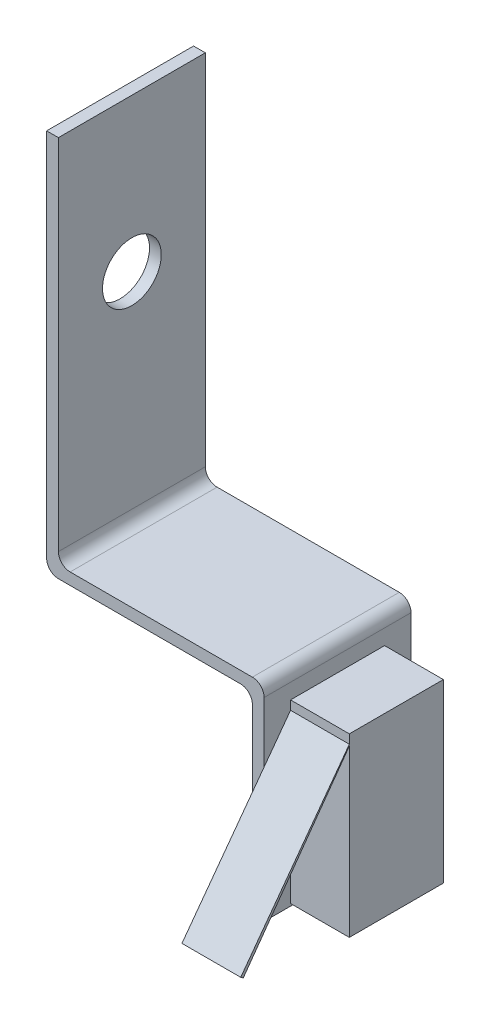
SolidWorks part; units mm, degrees
ref_plane "Alzado" through (0, 0, 0) normal (0, 0, 1) x (1, 0, 0)
ref_plane "Planta" through (0, 0, 0) normal (0, 1, 0) x (1, 0, 0)
ref_plane "Vista lateral" through (0, 0, 0) normal (1, 0, 0) x (0, 0, -1)
sketch "Sketch1" plane through (0, 0, 0) normal (0, 0, 1) x (1, 0, 0)
  line L0 (0, 0) -> (2, 0)
  line L1 (55, 0) -> (-55, 0) construction
  line L2 (2, 0) -> (2, -63)
  line L3 (2, -63) -> (37, -63)
  line L4 (37, -63) -> (37, -98)
  line L5 (37, -98) -> (35, -98)
  line L6 (35, -98) -> (35, -65)
  line L7 (35, -65) -> (0, -65)
  line L8 (0, -55) -> (0, 55) construction
  line L9 (0, -65) -> (0, 0)
  dimension "D1" = 2
  dimension "D2" = 63
  dimension "D3" = 2
  dimension "D4" = 35
  dimension "D5" = 35
  dimension "D6" = 2
extrude "Boss-Extrude1" add sketch "Sketch1" along normal blind 12.5 and the other way blind 12.5
hole_wizard "Ø10.0mm Dowel Hole1" positions "3DSketch1" profile "Sketch2" hole size "Ø10.0" standard "ISO" end condition through all
sketch3d "3DSketch1"
  point P0 (2, -26, 0)
  dimension "D1" = 0
  dimension "D2" = 26
sketch "Sketch2" plane through (2, -26, 0) normal (0, 1, 0) x (0, 0, -1)
  line L0 (0, 0) -> (0, 2)
  line L1 (0, 2) -> (5, 2)
  line L2 (5, 2) -> (5, 0)
  line L5 (5, 0) -> (0, 0)
  line L11 (0, -6.35) -> (0, 107.95) construction
  dimension "Thru Hole Dia." = 10
  dimension "Thru Hole Depth" = 2
fillet "Fillet1" radius 2 4 edges at (35, -65, 0) (0, -65, 0) (2, -63, 0) (37, -63, 0)
sketch "Sketch3" plane through (37, 0, 0) normal (1, 0, 0) x (0, 0, -1)
  line L0 (0, 20.35) -> (0, -20.35) construction
  line L1 (-8, -67.6044) -> (8, -67.6044)
  line L2 (-8, -67.6044) -> (-8, -97.6044)
  line L3 (-8, -97.6044) -> (8, -97.6044)
  line L4 (8, -67.6044) -> (8, -97.6044)
  dimension "D1" = 30
  dimension "D2" = 16
  dimension "D3" = 8
extrude "Boss-Extrude2" add sketch "Sketch3" along normal blind 10 contours L1 L4 L3 L2
sketch "Sketch4" plane through (47, 0, 0) normal (1, 0, 0) x (0, 0, -1)
  line L0 (-8, -69.1353) -> (-26.48, -94.2426)
  line L1 (-8, -67.6044) -> (-8, -97.6044) construction
  line L2 (-26.48, -94.2426) -> (-26.0466, -94.5593)
  line L3 (-26.0466, -94.5593) -> (-8, -69.4104)
  line L4 (-8, -67.6044) -> (-8, -97.6044) construction
  line L5 (-8, -69.4104) -> (-8, -69.1353)
extrude "Boss-Extrude3" add sketch "Sketch4" against normal blind 10
